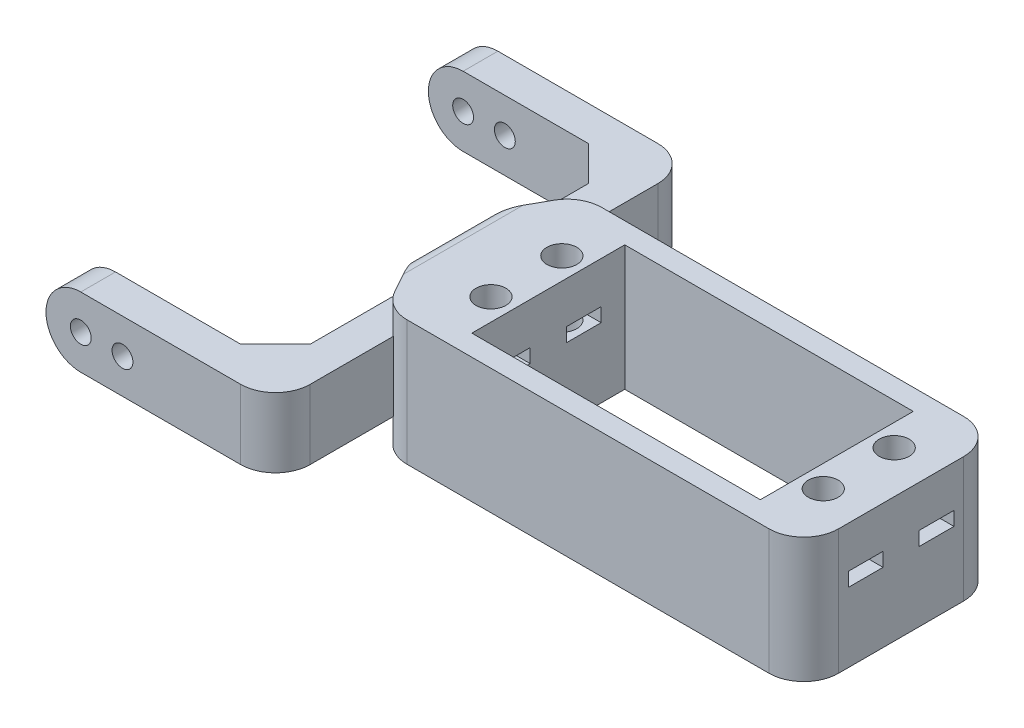
SolidWorks part; units mm, degrees
ref_plane "Plan de face" through (0, 0, 0) normal (0, 0, 1) x (1, 0, 0)
ref_plane "Plan de dessus" through (0, 0, 0) normal (0, 1, 0) x (1, 0, 0)
ref_plane "Plan de droite" through (0, 0, 0) normal (1, 0, 0) x (0, 0, -1)
sketch "Esquisse1" plane through (0, 0, 0) normal (0, 0, 1) x (1, 0, 0)
  line L1 (-30, -9) -> (30, -9)
  line L2 (-30, -9) -> (-30, 9)
  line L3 (-30, 9) -> (30, 9)
  line L4 (30, -9) -> (30, 9)
  line L5 (-30, -9) -> (30, 9) construction
  line L6 (-30, 9) -> (30, -9) construction
  point P0 (0, 0)
  dimension "D1" = 60
  dimension "D2" = 18
extrude "Boss.-Extru.1" add sketch "Esquisse1" along normal blind 28
sketch "Esquisse2" plane through (0, -9, 0) normal (0, -1, 0) x (1, 0, 0)
  line L0 (30, 0) -> (-30, 28) construction
  line L2 (20.75, 25) -> (-20.75, 25)
  line L3 (20.75, 25) -> (20.75, 3)
  line L4 (20.75, 3) -> (-20.75, 3)
  line L5 (-20.75, 25) -> (-20.75, 3)
  line L6 (20.75, 25) -> (-20.75, 3) construction
  line L7 (20.75, 3) -> (-20.75, 25) construction
  point P4 (0, 14)
  dimension "D1" = 41.5
  dimension "D2" = 22
extrude "Enlèv. mat.-Extru.1" cut sketch "Esquisse2" against normal blind 30
sketch "Esquisse3" plane through (0, -9, 0) normal (0, -1, 0) x (-1, 0, 0)
  circle A0 centre (23.9, -19.1) radius 2.15
  circle A1 centre (23.9, -8.9) radius 2.15
  circle A2 centre (-23.9, -8.9) radius 2.15
  circle A3 centre (-23.9, -19.1) radius 2.15
  dimension "D1" = 4.3
  dimension "D2" = 4.3
  dimension "D3" = 4.3
  dimension "D4" = 4.3
extrude "Enlèv. mat.-Extru.2" cut sketch "Esquisse3" against normal blind 30
sketch "Esquisse4" plane through (-30, 0, 0) normal (-1, 0, 0) x (0, 0, 1)
  line L0 (11.05, 9) -> (6.75, 9) construction
  line L1 (8.9, 9) -> (8.9, -9) construction
  line L2 (28, -9) -> (0, -9) construction
  line L3 (14, 9) -> (14, -9) construction
  line L4 (6.4, 1) -> (11.4, 1)
  line L5 (6.4, 1) -> (6.4, 3)
  line L6 (6.4, 3) -> (11.4, 3)
  line L7 (11.4, 1) -> (11.4, 3)
  line L8 (6.4, 1) -> (11.4, 3) construction
  line L9 (6.4, 3) -> (11.4, 1) construction
  line L10 (28, 9) -> (0, 9) construction
  line L11 (21.6, 1) -> (21.6, 3)
  line L12 (21.6, 1) -> (16.6, 1)
  line L13 (16.6, 1) -> (16.6, 3)
  line L14 (21.6, 3) -> (16.6, 3)
  point P8 (8.9, 2)
  dimension "D1" = 7
  dimension "D2" = 5
  dimension "D3" = 2
sketch "Esquisse5" plane through (-30, 0, 0) normal (-1, 0, 0) x (0, 0, 1)
  line L0 (0, 9) -> (28, -9) construction
  line L2 (9, -30) -> (19, -30)
  line L3 (9, -30) -> (9, 30)
  line L4 (9, 30) -> (19, 30)
  line L5 (19, -30) -> (19, 30)
  line L6 (9, -30) -> (19, 30) construction
  line L7 (9, 30) -> (19, -30) construction
  point P4 (14, 0)
  dimension "D1" = 10
  dimension "D2" = 60
extrude "Boss.-Extru.2" add sketch "Esquisse5" along normal blind 5
sketch "Esquisse6" plane through (-35, 0, 0) normal (-1, 0, 0) x (0, 0, 1)
  line L0 (9, 30) -> (19, 30)
  line L1 (9, 30) -> (9, 25)
  line L2 (19, 30) -> (19, 25)
  line L3 (9, 25) -> (19, 25)
  line L4 (9, -30) -> (19, -30)
  line L5 (9, -30) -> (9, -25)
  line L6 (19, -30) -> (19, -25)
  line L7 (9, -25) -> (19, -25)
  dimension "D1" = 5
  dimension "D2" = 5
extrude "Boss.-Extru.3" add sketch "Esquisse6" along normal blind 28
sketch "Esquisse7" plane through (0, 30, 0) normal (0, 1, 0) x (1, 0, 0)
  line L0 (-63, -14) -> (-30, -14) construction
  line L1 (-63, -19) -> (-63, -9) construction
  line L2 (-30, -19) -> (-30, -9) construction
  circle A0 centre (-58, -14) radius 1.5
  dimension "D1" = 3
  dimension "D2" = 5
extrude "Enlèv. mat.-Extru.4" cut sketch "Esquisse7" against normal through all both and the other way through all
fillet "Congé3" [suppressed] radius 5
sketch "Esquisse8" plane through (0, 0, 0) normal (0, 1, 0) x (1, 0, 0)
  line L0 (-30, -28) -> (-35, -19)
rib "Nervure11" sketch "Esquisse8" sketch "Esquisse8" thickness 18 extrusion direction parallel to sketch draft on no parameters "D1"=18
ref_plane "Plan1" through (0, 0, 14) normal (0, 0, 1) x (1, 0, 0)
mirror "Symétrie1" about plane through (0, 0, 14) normal (0, 0, 1) of "Nervure11"
fillet "Congé5" radius 5 4 edges at (-30, 0, 0) (30, 0, 0) (30, 0, 28) (-30, 0, 28)
ref_plane "Plan2" through (-30, 30, 9) normal (0, 0, -1) x (-1, 0, 0)
fillet "Congé6" radius 5 2 edges at (-30, 30, 14) (-30, -30, 14)
ref_plane "Plan3" through (0, 0, 14) normal (0, 0, 1) x (1, 0, 0)
sketch "Esquisse10" plane through (0, 0, 14) normal (0, 0, 1) x (1, 0, 0)
  line L0 (-40, 25) -> (-35, 20)
  line L1 (-63, 25) -> (-35, 25) construction
  line L2 (-35, 9) -> (-35, 25) construction
  dimension "D1" = 5
  dimension "D2" = 5
rib "Nervure12" sketch "Esquisse10" sketch "Esquisse10" thickness 10 extrusion direction parallel to sketch draft on no parameters "D1"=10
mirror "Symétrie2" about plane through (0, 0, 0) normal (0, 1, 0) of "Nervure12"
fillet "Congé7" radius 5 4 edges at (-63, -27.5, 9) (-63, -27.5, 19) (-63, 27.5, 9) (-63, 27.5, 19)
sketch "Esquisse12" plane through (-20.75, 0, 0) normal (1, 0, 0) x (0, 0, -1)
  line L0 (-16.95, 9) -> (-21.25, 9) construction
  line L1 (-25, 9) -> (-3, 9) construction
  line L2 (-16.95, -9) -> (-16.95, 9) construction
  line L3 (-21.25, 9) -> (-21.25, -9) construction
  line L4 (-19.1, 9) -> (-19.1, -9) construction
  line L5 (-25, -9) -> (-3, -9) construction
  line L6 (-14, 9) -> (-14, -9) construction
  line L7 (-21.6, 1) -> (-16.6, 1)
  line L8 (-21.6, 1) -> (-21.6, 3)
  line L9 (-21.6, 3) -> (-16.6, 3)
  line L10 (-16.6, 1) -> (-16.6, 3)
  line L11 (-21.6, 1) -> (-16.6, 3) construction
  line L12 (-21.6, 3) -> (-16.6, 1) construction
  line L13 (-6.4, 1) -> (-6.4, 3)
  line L14 (-6.4, 1) -> (-11.4, 1)
  line L15 (-11.4, 1) -> (-11.4, 3)
  line L16 (-6.4, 3) -> (-11.4, 3)
  point P6 (-19.1, 2)
  dimension "D1" = 5
  dimension "D2" = 2
  dimension "D3" = 7
extrude "Enlèv. mat.-Extru.5" cut sketch "Esquisse12" against normal blind 8 and the other way up to next
sketch "Esquisse13" plane through (0, -9, 0) normal (0, -1, 0) x (1, 0, 0)
  line L0 (14.75, 28) -> (14.75, 25)
  line L1 (14.75, 28) -> (-2.75, 28)
  line L2 (14.75, 25) -> (-2.75, 25)
  line L3 (-2.75, 28) -> (-2.75, 25)
  line L4 (-27.058, 28) -> (25, 28) construction
  line L5 (20.75, 25) -> (-20.75, 25) construction
  line L6 (20.75, 3) -> (20.75, 25) construction
  line L7 (-20.75, 25) -> (-20.75, 3) construction
  dimension "D1" = 6
  dimension "D2" = 18
extrude "Boss.-Extru.4" [suppressed] add sketch "Esquisse13" along normal blind 14
sketch "Esquisse14" [suppressed] plane through (0, 0, 25) normal (0, 0, -1) x (-1, 0, 0)
  line L0 (-14.75, -23) -> (-14.75, -19)
  line L1 (-14.75, -23) -> (2.75, -23)
  line L2 (-14.75, -19) -> (2.75, -19)
  line L3 (2.75, -23) -> (2.75, -19)
  line L4 (-14.75, -23) -> (-14.75, -9) construction
  line L6 (2.75, -23) -> (2.75, -9) construction
  dimension "D1" = 4
extrude "Boss.-Extru.5" [suppressed] add sketch "Esquisse14" along normal up to surface (25 mm away)
sketch "Esquisse15" [suppressed] plane through (0, -19, 0) normal (0, 1, 0) x (1, 0, 0)
  line L0 (14.75, 0) -> (-2.75, 0)
  line L1 (14.75, 0) -> (14.75, -3)
  line L2 (-2.75, 0) -> (-2.75, -3)
  line L3 (14.75, -3) -> (-2.75, -3)
  dimension "D1" = 3
extrude "Boss.-Extru.6" [suppressed] add sketch "Esquisse15" along normal up to surface (10 mm away)
sketch "Esquisse16" [suppressed] plane through (0, -23, 0) normal (0, -1, 0) x (-1, 0, 0)
  circle A0 centre (-10, -12.5) radius 1.5
  dimension "D1" = 3
extrude "Enlèv. mat.-Extru.6" [suppressed] cut sketch "Esquisse16" against normal blind 12
sketch "Esquisse17" plane through (0, 0, 0) normal (0, 0, 1) x (1, 0, 0)
  line L0 (-35, 0) -> (-63.904, 0) construction
  line L1 (-35, 9) -> (-35, -9) construction
sketch "Esquisse19" plane through (0, 0, 14) normal (0, 0, 1) x (1, 0, 0)
  line L0 (-35, 0) -> (-134.3013, 0) construction
pattern_circular "Répétition circulaire1" count 3 every 90 about axis through (-35, 0, 14) along (-1, 0, 0) of "Boss.-Extru.2", "Boss.-Extru.3", "Enlèv. mat.-Extru.4" reverse direction yes
sketch "Esquisse20" plane through (0, 5, 0) normal (0, 1, 0) x (1, 0, 0)
  line L0 (-31.4288, -25.4282) -> (-35, -19) construction
  line L1 (-35, -19) -> (-35, -39) construction
  line L2 (-35, -39) -> (-63, -39) construction
  line L3 (-63, -39) -> (-63, -44) construction
  line L4 (-63, -44) -> (-30, -44) construction
  line L5 (-30, -44) -> (-30, -27.0428) construction
  line L6 (-35, -9) -> (-31.4288, -2.5718) construction
  line L7 (-30, -0.9572) -> (-30, 16) construction
  line L8 (-30, 16) -> (-63, 16) construction
  line L9 (-63, 16) -> (-63, 11) construction
  line L10 (-63, 11) -> (-35, 11) construction
  line L11 (-35, 11) -> (-35, -9) construction
  line L12 (-31.4288, -25.4282) -> (-35, -19)
  line L13 (-35, -19) -> (-35, -39)
  line L14 (-35, -39) -> (-63, -39)
  line L15 (-63, -39) -> (-63, -44)
  line L16 (-63, -44) -> (-30, -44)
  line L17 (-30, -44) -> (-30, -27.0428)
  line L18 (-35, -9) -> (-31.4288, -2.5718)
  line L19 (-30, -0.9572) -> (-30, 16)
  line L20 (-30, 16) -> (-63, 16)
  line L21 (-63, 16) -> (-63, 11)
  line L22 (-63, 11) -> (-35, 11)
  line L23 (-35, 11) -> (-35, -9)
  arc A0 (-31.4288, -25.4282) -> (-30, -27.0428) centre (-27.058, -23) ccw construction
  arc A1 (-30, -0.9572) -> (-31.4288, -2.5718) centre (-27.058, -5) ccw construction
  arc A2 (-31.4288, -25.4282) -> (-30, -27.0428) centre (-27.058, -23) ccw
  arc A3 (-30, -0.9572) -> (-31.4288, -2.5718) centre (-27.058, -5) ccw
sketch "Esquisse21" plane through (0, 0, 9) normal (0, 0, -1) x (-1, 0, 0)
  line L0 (63, -25) -> (40, -25) construction
  line L1 (40, -25) -> (35, -20) construction
  line L2 (35, -20) -> (35, -9) construction
  line L3 (35, -9) -> (30, -9) construction
  line L4 (30, -9) -> (30, -30) construction
  line L5 (30, -30) -> (63, -30) construction
  line L6 (63, -30) -> (63, -25) construction
  line L7 (35, 20) -> (40, 25) construction
  line L8 (40, 25) -> (63, 25) construction
  line L9 (63, 25) -> (63, 30) construction
  line L10 (63, 30) -> (30, 30) construction
  line L11 (30, 30) -> (30, 9) construction
  line L12 (30, 9) -> (35, 9) construction
  line L13 (35, 9) -> (35, 20) construction
  line L14 (63, -25) -> (40, -25)
  line L15 (40, -25) -> (35, -20)
  line L16 (35, -20) -> (35, -9)
  line L17 (35, -9) -> (30, -9)
  line L18 (30, -9) -> (30, -30)
  line L19 (30, -30) -> (63, -30)
  line L20 (63, -30) -> (63, -25)
  line L21 (35, 20) -> (40, 25)
  line L22 (40, 25) -> (63, 25)
  line L23 (63, 25) -> (63, 30)
  line L24 (63, 30) -> (30, 30)
  line L25 (30, 30) -> (30, 9)
  line L26 (30, 9) -> (35, 9)
  line L27 (35, 9) -> (35, 20)
extrude "Enlèv. mat.-Extru.8" cut sketch "Esquisse21" against normal through all both and the other way through all
fillet "Congé8" radius 5 2 edges at (-30, 0, 44) (-30, 0, -16)
fillet "Congé10" radius 5 4 edges at (-63, 5, -13.5) (-63, -5, -13.5) (-63, -5, 41.5) (-63, 5, 41.5)
fillet "Congé12" radius 2 2 edges at (-35, 9, 14) (-35, -9, 14)
sketch "Esquisse22" plane through (0, 0, 0) normal (0, 1, 0) x (1, 0, 0)
  line L0 (-40, 11) -> (-35, 6)
  line L2 (-58, 11) -> (-35, 11) construction
  line L3 (-35, -9) -> (-35, 11) construction
  dimension "D1" = 5
  dimension "D2" = 5
rib "Nervure13" sketch "Esquisse22" sketch "Esquisse22" thickness 10 extrusion direction parallel to sketch draft on no parameters "D1"=10
ref_plane "Plan4" through (0, 0, 14) normal (0, 0, -1) x (-1, 0, 0)
mirror "Symétrie3" about plane through (0, 0, 14) normal (0, 0, -1) of "Nervure13"
sketch "Esquisse23" [suppressed] plane through (0, 30, 0) normal (0, 1, 0) x (1, 0, 0)
  line L0 (-35, -14) -> (-63, -14) construction
  line L1 (-35, -19) -> (-35, -9) construction
  circle A0 centre (-51, -14) radius 1.5
  dimension "D1" = 3
  dimension "D2" = 12
extrude "Enlèv. mat.-Extru.9" [suppressed] cut sketch "Esquisse23" against normal through all
fillet "Congé13" [suppressed] radius 2
sketch "Esquisse24" plane through (0, 0, -16) normal (0, 0, -1) x (-1, 0, 0)
  line L0 (63, 0) -> (30, 0) construction
  line L1 (30, 5) -> (30, -5) construction
  circle A0 centre (52, 0) radius 1.5
  circle A1 centre (58, 0) radius 1.5 construction
  dimension "D2" = 3
  dimension "D1" = 6
extrude "Enlèv. mat.-Extru.10" cut sketch "Esquisse24" against normal through all both and the other way through all
